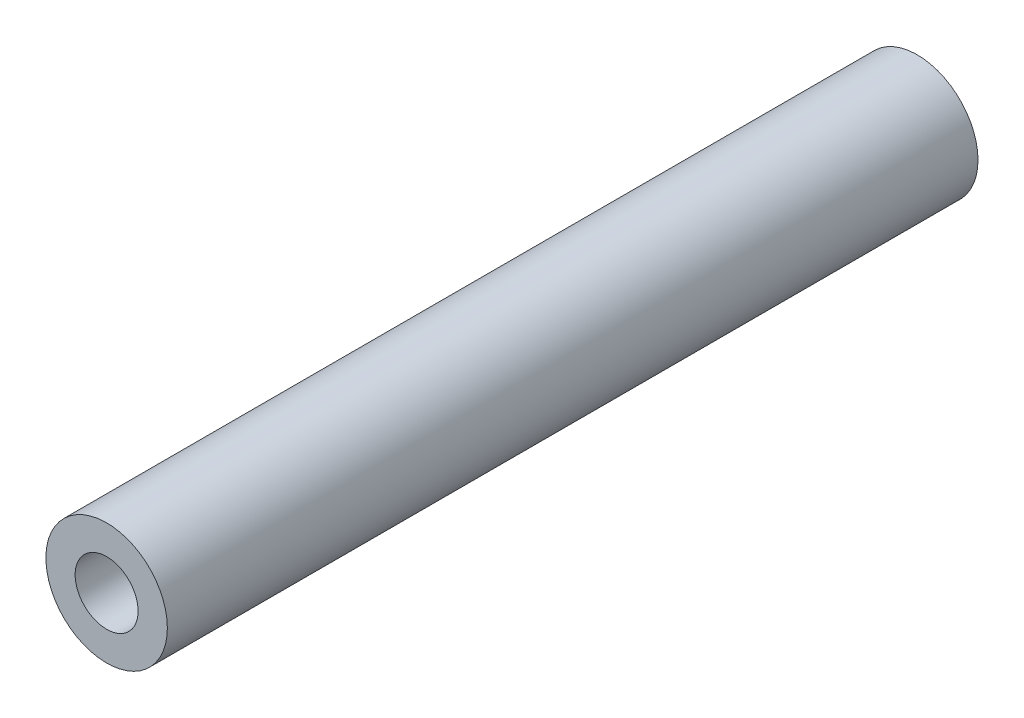
SolidWorks part; units mm, degrees
material "Plain Carbon Steel"
ref_plane "Front Plane" through (0, 0, 0) normal (0, 0, 1) x (1, 0, 0)
ref_plane "Top Plane" through (0, 0, 0) normal (0, 1, 0) x (1, 0, 0)
ref_plane "Right Plane" through (0, 0, 0) normal (1, 0, 0) x (0, 0, -1)
sketch "Sketch1" plane through (0, 0, 0) normal (0, 0, 1) x (1, 0, 0)
  circle A0 centre (0, 0) radius 5
  dimension "D1" = 10
extrude "Boss-Extrude1" add sketch "Sketch1" along normal blind 66.73
hole_wizard "#6 (0.204) Diameter Hole1" positions "Sketch2" profile "Sketch3" hole size "#6" standard "ANSI Inch"
sketch "Sketch2" plane through (0, 0, 0) normal (0, 0, -1) x (-1, 0, 0)
  point P0 (0, 0)
sketch "Sketch3" plane through (0, 0, 0) normal (1, 0, 0) x (0, 1, 0)
  line L0 (0, 0) -> (0, 31.5567)
  line L1 (0, 31.5567) -> (2.5908, 30)
  line L2 (2.5908, 30) -> (2.5908, 0)
  line L5 (2.5908, 0) -> (0, 0)
  line L10 (0, 31.5567) -> (-2.5908, 30) construction
  line L11 (0, -6.35) -> (0, 107.95) construction
  dimension "Hole Dia." = 5.1816
  dimension "Hole Depth" = 30
  dimension "Drill Angle" = 118
hole_wizard "#6 (0.204) Diameter Hole2" positions "Sketch4" profile "Sketch5" hole size "#6" standard "ANSI Inch"
sketch "Sketch4" plane through (0, 0, 66.73) normal (0, 0, 1) x (1, 0, 0)
  point P0 (0, 0)
sketch "Sketch5" plane through (0, 0, 66.73) normal (1, 0, 0) x (0, -1, 0)
  line L0 (0, 0) -> (0, 31.5567)
  line L1 (0, 31.5567) -> (2.5908, 30)
  line L2 (2.5908, 30) -> (2.5908, 0)
  line L5 (2.5908, 0) -> (0, 0)
  line L10 (0, 31.5567) -> (-2.5908, 30) construction
  line L11 (0, -6.35) -> (0, 107.95) construction
  dimension "Hole Dia." = 5.1816
  dimension "Hole Depth" = 30
  dimension "Drill Angle" = 118
